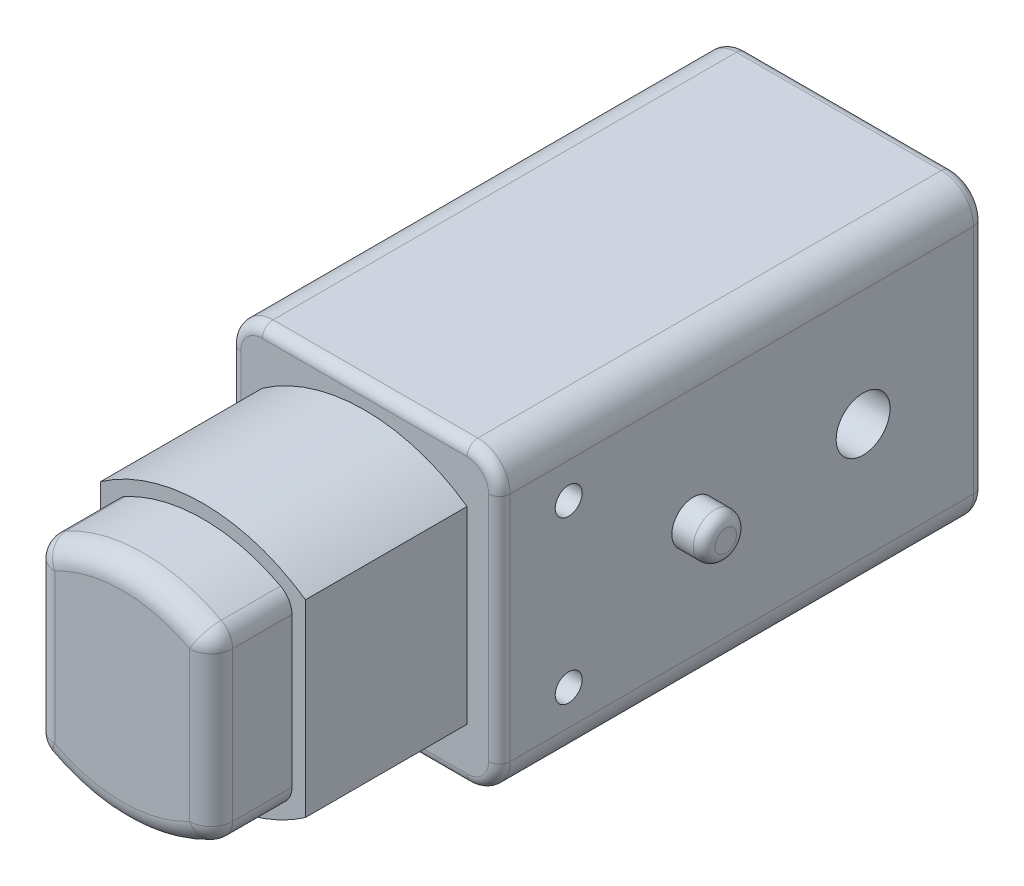
SolidWorks part; units mm, degrees
ref_plane "Front Plane" through (0, 0, 0) normal (0, 0, 1) x (1, 0, 0)
ref_plane "Top Plane" through (0, 0, 0) normal (0, 1, 0) x (1, 0, 0)
ref_plane "Right Plane" through (0, 0, 0) normal (1, 0, 0) x (0, 0, -1)
sketch "MotorMainSketch" plane through (0, 0, 0) normal (0, 0, 1) x (1, 0, 0)
  line L1 (-9.5, 13.75) -> (9.5, 13.75)
  line L2 (-12.5, 10.75) -> (-12.5, -10.75)
  line L3 (-9.5, -13.75) -> (9.5, -13.75)
  line L4 (12.5, 10.75) -> (12.5, -10.75)
  line L5 (-12.5, 13.75) -> (12.5, -13.75) construction
  line L6 (-12.5, -13.75) -> (12.5, 13.75) construction
  arc A0 (12.5, 10.75) -> (9.5, 13.75) centre (9.5, 10.75) ccw
  arc A2 (12.5, -10.75) -> (9.5, -13.75) centre (9.5, -10.75) cw
  arc A3 (-9.5, 13.75) -> (-12.5, 10.75) centre (-9.5, 10.75) ccw
  arc A4 (-9.5, -13.75) -> (-12.5, -10.75) centre (-9.5, -10.75) cw
  point P1 (0, 0)
  dimension "D1" = 3
  dimension "width1" = 25
  dimension "Width2" = 27.5
extrude "MotorBody1" add sketch "MotorMainSketch" along normal blind 45
sketch "Motorsketch" plane through (0, 0, 45) normal (0, 0, 1) x (1, 0, 0)
  line L0 (0, 11.75) -> (0, 8.75) construction
  line L1 (-9.5, 8.75) -> (9.5, 8.75) construction
  line L2 (-9.5, 8.75) -> (-9.5, -8.75)
  line L3 (-9.5, -8.75) -> (9.5, -8.75) construction
  line L4 (9.5, 8.75) -> (9.5, -8.75)
  line L5 (-9.5, 8.75) -> (9.5, -8.75) construction
  line L6 (-9.5, -8.75) -> (9.5, 8.75) construction
  line L7 (12.5, -10.75) -> (12.5, 10.75) construction
  line L8 (9.5, 13.75) -> (-9.5, 13.75) construction
  arc A0 (-9.5, 8.75) -> (9.5, 8.75) centre (0, -4.7917) cw
  arc A1 (-9.5, -8.75) -> (9.5, -8.75) centre (0, 4.7917) ccw
  point P0 (0, 0)
  point P17 (0, 13.75)
  dimension "D1" = 3
  dimension "D2" = 2
  dimension "D3" = 3
extrude "MotorBody2" add sketch "Motorsketch" along normal blind 15
sketch "side engravement sketch" plane through (12.5, 0, 0) normal (1, 0, 0) x (0, 0, -1)
  line L0 (0, 0) -> (-45, 0) construction
  line L1 (-45, -8.75) -> (-45, 8.75) construction
  line L2 (-38.5714, 7.5) -> (-38.5714, -7.5) construction
  circle A0 centre (-38.5714, 7.5) radius 1.25
  circle A1 centre (-38.5714, -7.5) radius 1.25
  circle A2 centre (-27, 0) radius 2
  circle A3 centre (-11.25, 0) radius 2.5
  point P5 (-38.5714, 0)
  dimension "D1" = 15
  dimension "D3" = 2.5
  dimension "D5" = 4
  dimension "D6" = 5
  dimension "D2" = 6.4286
  dimension "D4" = 18
  dimension "D7" = 11.25
extrude "Cut-Extrude1" cut sketch "side engravement sketch" against normal through all contours A0 | A1 | A3 region at (12.5, 7.5, 38.5714) region at (12.5, -7.5, 38.5714) region at (12.5, 0, 11.25)
extrude "Boss-Extrude3" add sketch "side engravement sketch<3>" along normal blind 3 contours A2
sketch "side engravement sketch<3>" plane through (12.5, 0, 0) normal (1, 0, 0) x (0, 0, -1) same geometry as "side engravement sketch"
sketch "Sketch4" plane through (0, 0, 0) normal (0, 0, -1) x (-1, 0, 0)
  line L0 (-12.5, 0) -> (12.5, 0) construction
  line L1 (-12.5, -10.75) -> (-12.5, 10.75) construction
  line L2 (12.5, 10.75) -> (12.5, -10.75) construction
  line L3 (0, 13.75) -> (0, -13.75) construction
  line L4 (-9.5, 13.75) -> (9.5, 13.75) construction
  line L5 (9.5, -13.75) -> (-9.5, -13.75) construction
  circle A0 centre (0, 0) radius 3.5
  dimension "D1" = 7
extrude "Boss-Extrude5" add sketch "Sketch4" along normal blind 5
fillet "Fillet1" radius 1 18 edges at (11.6213, -12.8713, 45) (0, -13.75, 45) (-11.6213, -12.8713, 45) (-12.5, 0, 45) (-11.6213, 12.8713, 45) (0, 13.75, 45) (11.6213, 12.8713, 45) (11.6213, 12.8713, 0) (12.5, 0, 0) (11.6213, -12.8713, 0) (0, -13.75, 0) (-11.6213, -12.8713, 0) (-12.5, 0, 0) (-11.6213, 12.8713, 0) (12.5, 0, 45) (15.5, 2, 27) (-3.5, 0, -5) (0, 13.75, 0)
sketch "Sketch5" plane through (0, 0, 60) normal (0, 0, 1) x (1, 0, 0)
  line L0 (9.5, -8.75) -> (9.5, 8.75) construction
  line L1 (-9.5, 8.75) -> (-9.5, -8.75) construction
  line L2 (-9.5, 8.75) -> (-9.5, -8.75)
  line L3 (9.5, -8.75) -> (9.5, 8.75)
  line L4 (-8.25, 8.0836) -> (-8.25, -8.0836)
  line L5 (8.25, -8.0836) -> (8.25, 8.0836)
  arc A0 (9.5, 8.75) -> (-9.5, 8.75) centre (0, -4.7917) ccw construction
  arc A1 (-9.5, -8.75) -> (9.5, -8.75) centre (0, 4.7917) ccw construction
  arc A2 (-9.5, -8.75) -> (9.5, -8.75) centre (0, 4.7917) ccw
  arc A3 (9.5, 8.75) -> (-9.5, 8.75) centre (0, -4.7917) ccw
  arc A4 (-8.25, -8.0836) -> (8.25, -8.0836) centre (0, 4.7917) ccw
  arc A5 (8.25, 8.0836) -> (-8.25, 8.0836) centre (0, -4.7917) ccw
  dimension "D1" = 1.25
extrude "Boss-Extrude6" add sketch "Sketch5" along normal blind 7.5 contours L5 A5 L4 A4 region at (0, 0, 60)
fillet "Fillet3" radius 2 8 edges at (8.25, -8.0836, 63.75) (0, -10.5, 67.5) (-8.25, -8.0836, 63.75) (-8.25, 0, 67.5) (-8.25, 8.0836, 63.75) (0, 10.5, 67.5) (8.25, 0, 67.5) (8.25, 8.0836, 63.75)
equation "\"motorlength1A\"= 4.5"
equation "\"D1@MotorBody1\" = \"motorlength1A\""
equation "\"motorlength2\"= \"motorlength1A\" / 3"
equation "\"D1@MotorBody2\" = \"motorlength2\""
equation "\"motorwidth\"=2.5"
equation "\"width1@MotorMainSketch\"=\"motorwidth\""
equation "\"motorheight\"=2.75"
equation "\"Width2@MotorMainSketch\"=\"motorheight\""
equation "\"D2@side engravement sketch\"=\"motorlength1A\"/7"
equation "\"MotorScrewhole\"= 0.25"
equation "\"D3@side engravement sketch\"=\"MotorScrewhole\""
equation "\"D4@side engravement sketch\"=\"motorlength1A\"/2.5"
equation "\"D7@side engravement sketch\"=\"motorlength1A\"/4"
